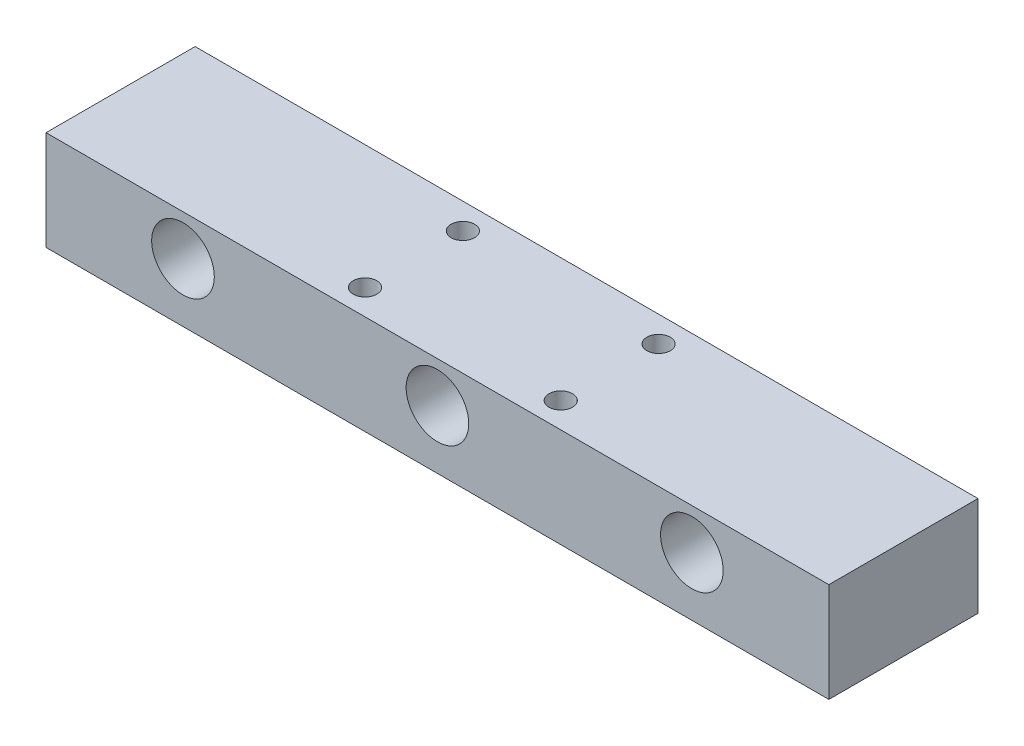
SolidWorks part; units mm, degrees
ref_plane "Front Plane" through (0, 0, 0) normal (0, 0, 1) x (1, 0, 0)
ref_plane "Top Plane" through (0, 0, 0) normal (0, 1, 0) x (1, 0, 0)
ref_plane "Right Plane" through (0, 0, 0) normal (1, 0, 0) x (0, 0, -1)
sketch "Sketch1" plane through (0, 0, 0) normal (0, 1, 0) x (1, 0, 0)
  line L1 (0, 0) -> (400, 0)
  line L2 (0, 0) -> (0, 76.2)
  line L3 (0, 76.2) -> (400, 76.2)
  line L4 (400, 0) -> (400, 76.2)
  dimension "D1" = 76.2
  dimension "D2" = 400
extrude "Boss-Extrude1" add sketch "Sketch1" along normal blind 50.8
sketch "Sketch3" plane through (0, 50.8, 0) normal (0, 1, 0) x (1, 0, 0)
  line L1 (0, 0) -> (200, 0)
  line L2 (0, 0) -> (0, 38)
  line L3 (0, 38) -> (200, 38)
  line L4 (200, 0) -> (200, 38)
  line L5 (150, 63) -> (250, 63)
  line L6 (150, 63) -> (150, 13)
  line L7 (150, 13) -> (250, 13)
  line L8 (250, 63) -> (250, 13)
  line L9 (150, 63) -> (250, 13) construction
  line L10 (150, 13) -> (250, 63) construction
  circle A0 centre (150, 63) radius 6
  circle A1 centre (150, 13) radius 6
  circle A2 centre (250, 63) radius 6
  circle A3 centre (250, 13) radius 6
  dimension "D1" = 200
  dimension "D2" = 38
  dimension "D3" = 100
  dimension "D4" = 50
extrude "Cut-Extrude2" cut sketch "Sketch3" against normal blind 50.8 contours A2 | A1 | A3 | A0
sketch "Sketch5" plane through (0, 0, 0) normal (0, 0, 1) x (1, 0, 0)
  line L0 (200, 30) -> (330, 30)
  line L1 (0, 0) -> (200, 0)
  line L2 (0, 0) -> (0, 30)
  line L4 (200, 0) -> (200, 30)
  line L5 (200, 30) -> (70, 30)
  circle A0 centre (200, 30) radius 16
  circle A1 centre (70, 30) radius 16
  circle A2 centre (330, 30) radius 16
  dimension "D3" = 130
  dimension "D1" = 30
  dimension "D2" = 200
  dimension "D4" = 130
extrude "Cut-Extrude3" cut sketch "Sketch5" against normal through all contours A1 | L0 A0 L5 | L4 A0 L0 | L5 A0 L4 | A2 region at (200, 36.7906, 0) region at (206.7906, 23.2094, 0) region at (193.2094, 23.2094, 0) region at (330, 45.5475, 0) region at (54.4525, 30, 0)
